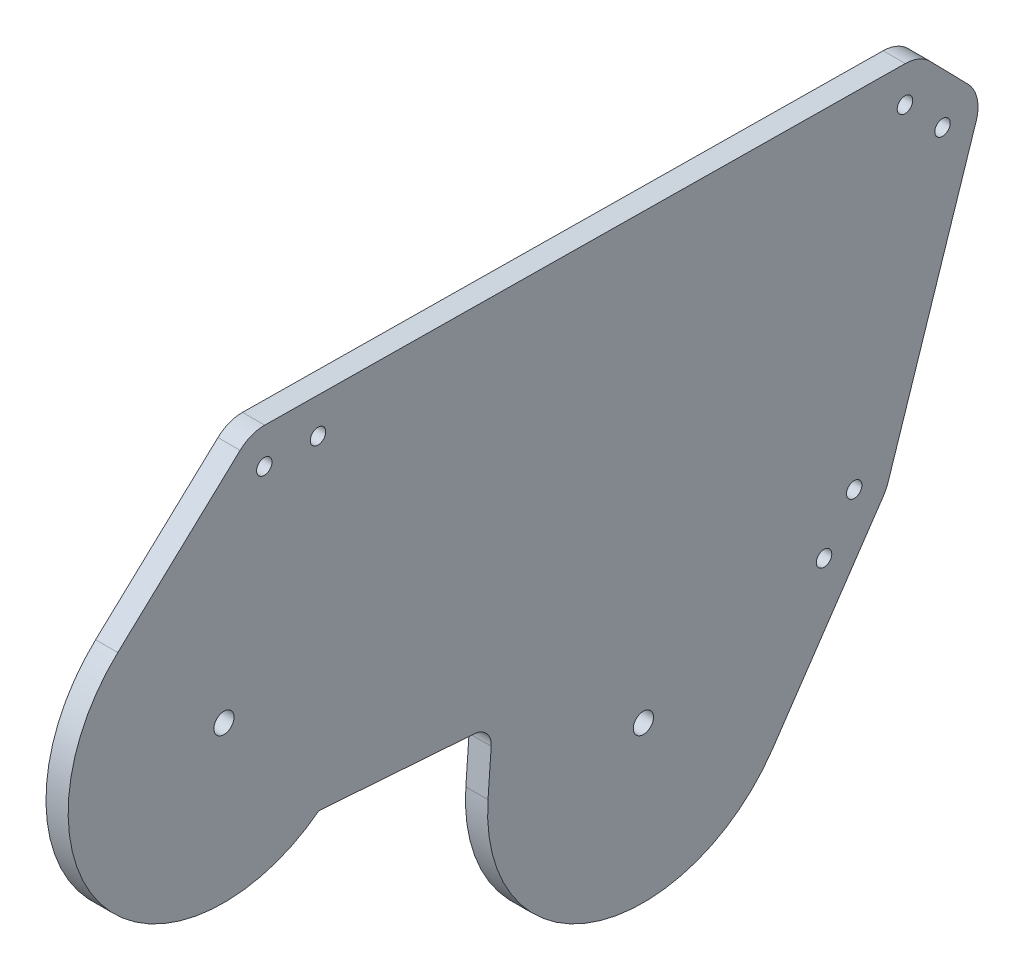
SolidWorks part; units mm, degrees
ref_plane "Front" through (0, 0, 0) normal (0, 0, 1) x (1, 0, 0)
ref_plane "Top" through (0, 0, 0) normal (0, 1, 0) x (1, 0, 0)
ref_plane "Right" through (0, 0, 0) normal (1, 0, 0) x (0, 0, -1)
ref_axis "side-side" through (80.9, 0, 0) along (-1, 0, 0)
ref_axis "up-down" through (0, 50, 0) along (0, -1, 0)
ref_axis "front-back" through (0, 0, -80.9) along (0, 0, 1)
sketch "Sketch1" plane through (0, 0, 0) normal (1, 0, 0) x (0, 0, -1)
  line L0 (-353.6017, 25.478) -> (-361.9919, 34.0573)
  line L1 (-374.4601, 39.7297) -> (-383.0705, -13.4376) construction
  line L4 (-498.5693, -42.5979) -> (-463.7881, -45.0971)
  line L5 (-460.8018, -59.3478) -> (-460.0851, -49.3735)
  line L7 (50, 0) -> (-50, 0) construction
  line L8 (-367.5783, 36.4445) -> (-510.6822, 38.0389)
  line L36 (-397.2737, -81.3642) -> (-372.435, -44.7034)
  line L37 (-371.4638, -42.7239) -> (-351.7341, 17.4554)
  line L40 (-516.1804, 35.9104) -> (-543.504, 10.4623)
  circle A1 centre (-359.2766, 19.9282) radius 1.7272
  circle A2 centre (-367.6668, 28.5075) radius 7.9375 construction
  arc A3 (-460.8018, -59.3478) -> (-397.2737, -81.3642) centre (-426.0872, -61.8422) ccw
  arc A4 (-543.504, 10.4623) -> (-498.5693, -42.5979) centre (-519.7834, -15.0065) ccw
  circle A7 centre (-379.0063, -40.2511) radius 7.9375 construction
  circle A8 centre (-510.7706, 30.1019) radius 7.9375 construction
  arc A12 (-361.9919, 34.0573) -> (-367.5783, 36.4445) centre (-367.6668, 28.5075) ccw
  circle A13 centre (-367.6668, 28.5075) radius 1.7272
  circle A14 centre (-510.7706, 30.1019) radius 1.7272
  circle A15 centre (-379.0063, -40.2511) radius 1.7272
  arc A16 (-353.6017, 25.478) -> (-351.7341, 17.4554) centre (-359.2766, 19.9282) cw
  circle A17 centre (-426.0872, -61.8422) radius 2.2542
  circle A19 centre (-519.7834, -15.0065) radius 2.2542
  arc A20 (-463.7881, -45.0971) -> (-460.0851, -49.3735) centre (-464.0748, -49.0868) cw
  arc A21 (-516.1804, 35.9104) -> (-510.6822, 38.0389) centre (-510.7706, 30.1019) cw
  arc A22 (-372.435, -44.7034) -> (-371.4638, -42.7239) centre (-379.0063, -40.2511) ccw
  circle A23 centre (-385.7372, -50.1857) radius 1.7272
  circle A25 centre (-498.7714, 29.9682) radius 1.7272
  point P10 (-30.1249, 32.6847)
  point P14 (0, 0)
  point P26 (-352.2461, 16.0239)
  point P28 (0, 0)
  point P39 (0, 0)
  point P47 (0, 0)
  dimension "D1" = 15.875
  dimension "D2" = 15.875
  dimension "D5" = 15.875
  dimension "D8" = 3.4544
  dimension "D9" = 94.11
  dimension "D10" = 14
  dimension "D11" = 4
  dimension "D12" = 15.875
  dimension "D14" = 7.9375
  dimension "D4" = 34.8041
  dimension "D15" = 34.8041
  dimension "D16" = 107.5919
  dimension "D3" = 4.5085
  dimension "D6" = 46
  dimension "D7" = 158.218
  dimension "D13" = 125
  dimension "D17" = 8.5
extrude "Boss-Extrude1" add sketch "Sketch1" against normal blind 4.953
